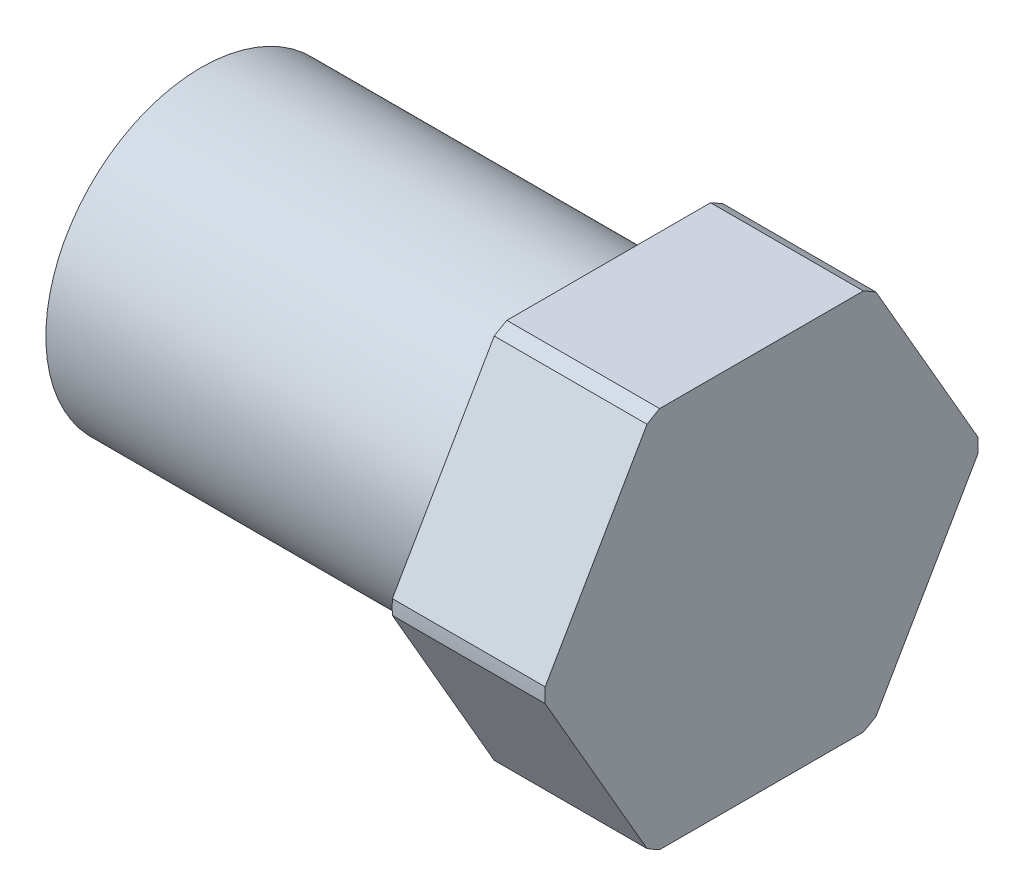
SolidWorks part; units mm, degrees
material "Water"
ref_plane "XY" through (0, 0, 0) normal (0, 0, 1) x (1, 0, 0)
ref_plane "XZ" through (0, 0, 0) normal (0, 1, 0) x (1, 0, 0)
ref_plane "YZ" through (0, 0, 0) normal (1, 0, 0) x (0, 0, -1)
ref_axis "X" through (-88.99, 0, 0) along (1, 0, 0)
ref_axis "Y" through (0, -55, 0) along (0, 1, 0)
ref_axis "Z" through (0, 0, 55) along (0, 0, -1)
sketch "Sketch1" plane through (0, 0, 0) normal (0, 0, 1) x (1, 0, 0)
  line L0 (0, 0) -> (0, 5.5562) construction
  line L1 (0, 10.795) -> (-7.62, 10.795)
  line L2 (-7.62, 10.795) -> (-7.62, 7.747)
  line L3 (-7.62, 7.747) -> (-27.94, 7.747)
  line L4 (-27.94, 7.747) -> (-27.94, 0)
  line L5 (-27.94, 0) -> (19.05, 0)
  line L6 (19.05, 0) -> (19.05, 5.5562)
  line L7 (19.05, 5.5562) -> (0, 5.5562)
  line L8 (0, 5.5562) -> (0, 10.795)
  dimension "D1" = 27.94
  dimension "D2" = 5.5562
  dimension "D3" = 7.747
  dimension "D4" = 10.795
  dimension "D5" = 7.62
  dimension "D6" = 19.05
revolve "Revolve1" add sketch "Sketch1" angle 360 about L5
sketch "Sketch2" plane through (-7.62, 0, 0) normal (-1, 0, 0) x (0, 0, 1)
  line L1 (-5.4993, 9.525) -> (-10.9985, 0)
  line L2 (-10.9985, 0) -> (-5.4993, -9.525)
  line L3 (-5.4993, -9.525) -> (5.4993, -9.525)
  line L4 (5.4993, -9.525) -> (10.9985, 0)
  line L5 (10.9985, 0) -> (5.4993, 9.525)
  line L6 (5.4993, 9.525) -> (-5.4993, 9.525)
  circle A0 centre (0, 0) radius 9.525 construction
  dimension "D1" = 19.05
extrude "Cut-Extrude1" cut sketch "Sketch2" against normal through all both and the other way through all flip side to cut
sketch "Sketch3" plane through (0, 0, 0) normal (1, 0, 0) x (0, 0, -1)
  circle A0 centre (0, 0) radius 5.5562 construction
  circle A1 centre (0, 0) radius 5.5562
extrude "Cut-Extrude2" cut sketch "Sketch3" along normal through all
